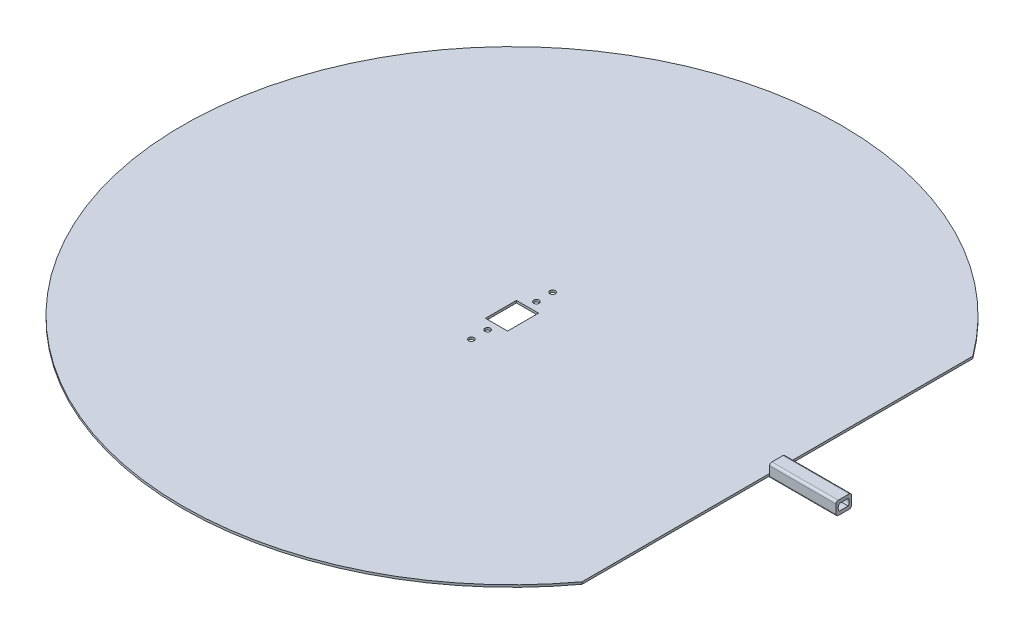
SolidWorks part; units mm, degrees
ref_plane "Plan de face" through (0, 0, 0) normal (0, 0, 1) x (1, 0, 0)
ref_plane "Plan de dessus" through (0, 0, 0) normal (0, 1, 0) x (1, 0, 0)
ref_plane "Plan de droite" through (0, 0, 0) normal (1, 0, 0) x (0, 0, -1)
sketch "Esquisse1" plane through (0, 0, 0) normal (0, 1, 0) x (1, 0, 0)
  line L0 (120, 90) -> (120, -90)
  line L2 (5, -7) -> (5, 7)
  line L3 (5, -7) -> (-5, -7)
  line L4 (-5, -7) -> (-5, 7)
  line L5 (5, 7) -> (-5, 7)
  line L6 (5, -7) -> (-5, 7) construction
  line L7 (-5, -7) -> (5, 7) construction
  circle A0 centre (0, 0) radius 150
  circle A1 centre (0, 0) radius 149
  circle A2 centre (0, -11) radius 1.25
  circle A3 centre (0, -18.4) radius 1.25
  circle A4 centre (0, 11) radius 1.25
  circle A5 centre (0, 18.4) radius 1.25
  dimension "D1" = 300
  dimension "D2" = 298
  dimension "D6" = 2.5
  dimension "D7" = 2.5
  dimension "D8" = 2.5
  dimension "D9" = 2.5
  dimension "D3" = 120
  dimension "D4" = 10
  dimension "D5" = 14
  dimension "D10" = 11
  dimension "D11" = 7.4
  dimension "D12" = 11
  dimension "D13" = 7.4
extrude "Boss.-Extru.1" add sketch "Esquisse1" against normal blind 2 contours A0
extrude "Enlèv. mat.-Extru.1" cut sketch "Esquisse1<4>" against normal blind 1 contours L0 A1 A5 A4 A3 A2 L5 L2 L3 L4 region at (-6.9493, 0, 0)
sketch "Esquisse1<4>" plane through (0, 0, 0) normal (0, 1, 0) x (1, 0, 0) same geometry as "Esquisse1"
extrude "Enlèv. mat.-Extru.2" cut sketch "Esquisse1<5>" against normal blind 13 contours L2 L5 L4 L3 | A2 | A3 | A4 | A5 region at (0, 0, 0) region at (0, 0, 11)
sketch "Esquisse1<5>" plane through (0, 0, 0) normal (0, 1, 0) x (1, 0, 0) same geometry as "Esquisse1"
sketch "Esquisse3" plane through (0, 0, 0) normal (0, 1, 0) x (1, 0, 0)
  line L0 (120, 88.3233) -> (120, -88.3233) construction
  line L1 (149.9592, -3.5) -> (120, -3.5)
  line L3 (149.9592, 3.5) -> (120, 3.5)
  line L4 (120, -3.5) -> (120, 3.5)
  line L5 (149.9594, -3.4905) -> (120, 3.5) construction
  line L6 (149.9594, 3.4905) -> (120, -3.5) construction
  circle A2 centre (0, 0) radius 150
  point P0 (135, 0)
  circle M5 centre (0, 0) radius 150
  arc M6 (120, -88.3233) -> (120, 88.3233) centre (0, 0) cw
  line M7 (120, 88.3233) -> (120, -88.3233)
  dimension "D1" = 7
extrude "Boss.-Extru.3" add sketch "Esquisse3" along normal blind 3 contours L3 L1 M5 M7 region at (134.9932, 0, 0)
extrude "Boss.-Extru.4" add sketch "Esquisse3<2>" against normal blind 3 contours L3 L1 M5 M7 region at (134.9932, 0, 0)
sketch "Esquisse3<2>" plane through (0, 0, 0) normal (0, 1, 0) x (1, 0, 0) same geometry as "Esquisse3"
sketch "Esquisse4" plane through (120, 0, 0) normal (1, 0, 0) x (0, 0, -1)
  line L0 (-2, 1.5) -> (2, 1.5)
  line L1 (-2, -1.5) -> (2, -1.5)
  arc A0 (-2, 1.5) -> (-2, -1.5) centre (0, 0) ccw
  arc A1 (2, -1.5) -> (2, 1.5) centre (0, 0) ccw
  dimension "D1" = 5
  dimension "D2" = 1.5
  dimension "D3" = 1.5
extrude "Enlèv. mat.-Extru.3" cut sketch "Esquisse4" along normal blind 50 contours L0 A1 L1 A0
fillet "Congé1" radius 1 4 edges at (134.9796, -3, -3.5) (134.9796, -3, 3.5) (134.9796, 3, 3.5) (134.9796, 3, -3.5)
sketch "Esquisse5" plane through (0, 0, 0) normal (1, 0, 0) x (0, 0, -1)
  circle A0 centre (0, 0) radius 1
  dimension "D1" = 2
extrude "Enlèv. mat.-Extru.4" cut sketch "Esquisse5" against normal blind 180
extrude "Enlèv. mat.-Extru.5" cut sketch "Esquisse3<4>" against normal through all contours L3 L1 M5 M7 M6 region at (-149.5758, 0, 0)
sketch "Esquisse3<4>" plane through (0, 0, 0) normal (0, 1, 0) x (1, 0, 0) same geometry as "Esquisse3"
sketch "Esquisse7" plane through (120, 0, 0) normal (-1, 0, 0) x (0, 0, 1)
  line L1 (-3.5, -2) -> (3.5, -2)
  line L2 (-3.5, -2) -> (-3.5, -3)
  line L3 (-3.5, -3) -> (3.5, -3)
  line L4 (3.5, -2) -> (3.5, -3)
extrude "Boss.-Extru.5" add sketch "Esquisse7" along normal blind 20
fillet "Congé3" radius 1 3 edges at (100, -3, 0) (110, -3, -3.5) (110, -3, 3.5)
